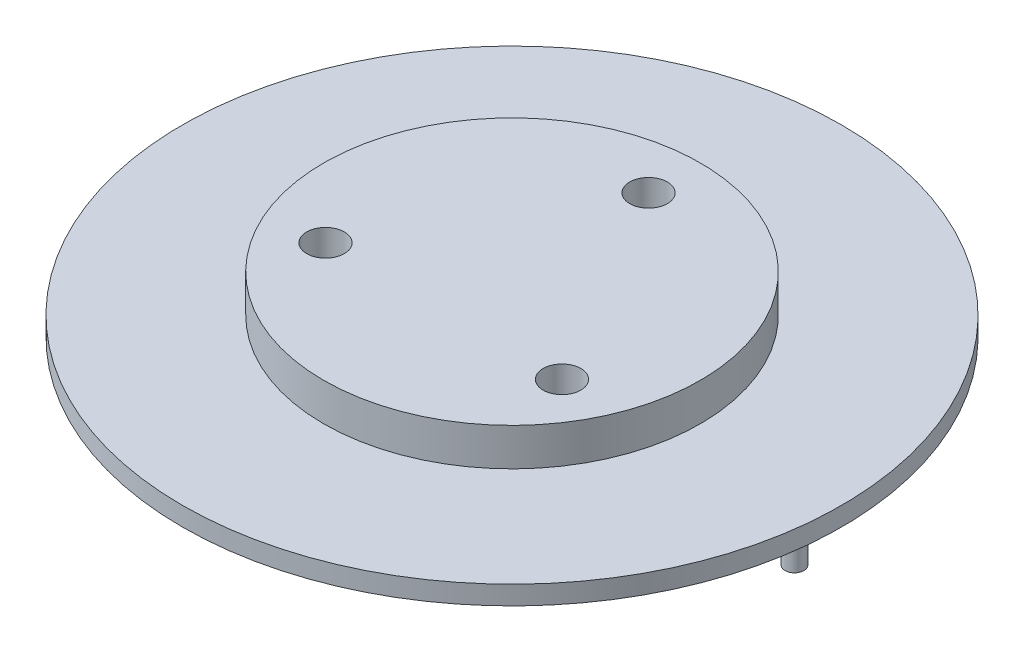
SolidWorks part; units mm, degrees
ref_plane "前基準面" through (0, 0, 0) normal (0, 0, 1) x (1, 0, 0)
ref_plane "上基準面" through (0, 0, 0) normal (0, 1, 0) x (1, 0, 0)
ref_plane "右基準面" through (0, 0, 0) normal (1, 0, 0) x (0, 0, -1)
sketch "草圖1" plane through (0, 0, 0) normal (0, 1, 0) x (1, 0, 0)
  line L0 (0, 0) -> (0, 72.5) construction
  line L1 (0, 0) -> (-62.7868, -36.25) construction
  line L2 (0, 0) -> (62.7868, -36.25) construction
  circle A0 centre (0, 0) radius 72.5 construction
  circle A1 centre (0, 72.5) radius 10
  circle A2 centre (62.7868, -36.25) radius 10
  circle A3 centre (-62.7868, -36.25) radius 10
  circle A4 centre (0, 0) radius 40 construction
  circle A5 centre (0, 0) radius 100
  dimension "D3" = 145
  dimension "D4" = 20
  dimension "D5" = 80
  dimension "D6" = 200
  dimension "D1" = 120
  dimension "D2" = 120
extrude "填料-伸長1" add sketch "草圖1" along normal blind 20
sketch "草圖2" plane through (0, 0, 0) normal (0, -1, 0) x (1, 0, 0)
  line L0 (-150, 0) -> (150, 0) construction
  circle A0 centre (-150, 0) radius 5
  circle A1 centre (150, 0) radius 5
  circle A2 centre (0, 0) radius 175
  point P3 (0, 0)
  dimension "D2" = 10
  dimension "D3" = 350
  dimension "D1" = 300
extrude "填料-伸長2" add sketch "草圖2" along normal blind 10
sketch "草圖3" plane through (0, -10, 0) normal (0, -1, 0) x (1, 0, 0)
  circle A0 centre (-150, 0) radius 5 construction
  circle A1 centre (-150, 0) radius 5
  circle A2 centre (150, 0) radius 5 construction
  circle A3 centre (150, 0) radius 5
extrude "填料-伸長3" add sketch "草圖3" along normal blind 30 and the other way up to surface (10 mm away) other way up to face at (0, 0, 100)
